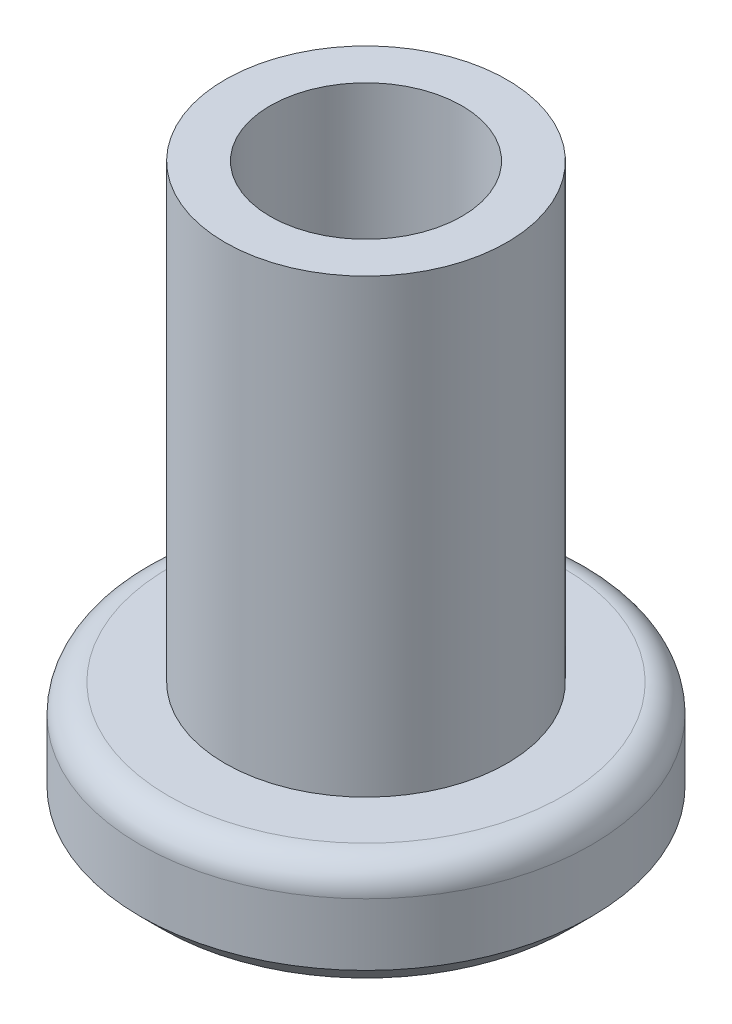
SolidWorks part; units mm, degrees
ref_plane "Front Plane" through (0, 0, 0) normal (0, 0, 1) x (1, 0, 0)
ref_plane "Top Plane" through (0, 0, 0) normal (0, 1, 0) x (1, 0, 0)
ref_plane "Right Plane" through (0, 0, 0) normal (1, 0, 0) x (0, 0, -1)
sketch "Sketch1" plane through (0, 0, 0) normal (0, 1, 0) x (1, 0, 0)
  circle A0 centre (0, 0) radius 1.7
  circle A1 centre (0, 0) radius 2.5
  circle A2 centre (0, 0) radius 4
  circle A3 centre (0, 0) radius 3
  dimension "D1" = 3.4
  dimension "D2" = 5
  dimension "D3" = 8
  dimension "D4" = 6
extrude "Boss-Extrude1" add sketch "Sketch1" along normal blind 8 contours A1 A0 region at (-2.4293, 0, 0)
extrude "Boss-Extrude2" add sketch "Sketch1<3>" against normal blind 2 contours A1 A0 | A3 A1 | A2 A3 region at (-2.4293, 0, 0) region at (-3.8869, 0, 0) region at (-2.9151, 0, 0)
sketch "Sketch1<3>" plane through (0, 0, 0) normal (0, 1, 0) x (1, 0, 0) same geometry as "Sketch1"
fillet "Fillet1" radius 0.5 1 edges at (0, 0, 4)
chamfer "Chamfer1" distance 0.4 angle 45 2 edges at (0, -2, 4) (0, -2, 1.7)
